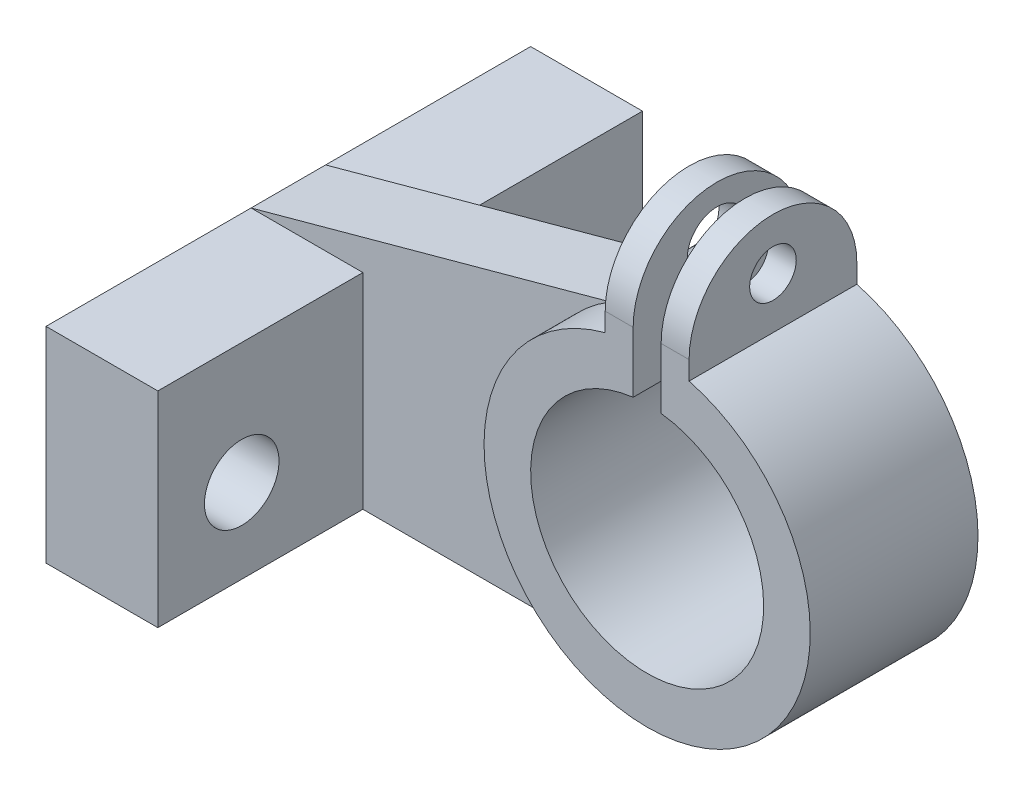
SolidWorks part; units mm, degrees
material "ABS"
ref_plane "Front Plane" through (0, 0, 0) normal (0, 0, 1) x (1, 0, 0)
ref_plane "Top Plane" through (0, 0, 0) normal (0, 1, 0) x (1, 0, 0)
ref_plane "Right Plane" through (0, 0, 0) normal (1, 0, 0) x (0, 0, -1)
sketch "Sketch1" plane through (0, 0, 0) normal (0, 0, 1) x (1, 0, 0)
  line L0 (-1.5, 27.9097) -> (-1.5, 12.4097)
  line L5 (-1.5, 27.9097) -> (-4.5, 27.9097)
  line L8 (-4.5, 27.9097) -> (-4.5, 16.9115)
  line L9 (1.5, 27.9097) -> (4.5, 27.9097)
  line L12 (4.5, 27.9097) -> (4.5, 16.9115)
  line L13 (1.5, 27.9097) -> (1.5, 12.4097)
  line L14 (-47.5, 4.5) -> (-8.9183, 15.057)
  line L15 (0, -17.5) -> (-41.5, -17.5)
  line L20 (-41.5, 4.5) -> (-41.5, -17.5)
  line L21 (-41.5, -17.5) -> (-47.5, -17.5)
  line L23 (-41.5, 4.5) -> (-47.5, 4.5)
  line L24 (-47.5, -17.5) -> (-47.5, 4.5)
  arc A0 (-1.5, 12.4097) -> (1.5, 12.4097) centre (0, 0) ccw
  arc A1 (-4.5, 16.9115) -> (4.5, 16.9115) centre (0, 0) ccw
  dimension "D1" = 25
  dimension "D2" = 5
  dimension "D3" = 3
  dimension "D4" = 9
  dimension "D5" = 3
  dimension "D6" = 3
  dimension "D7" = 15.5
  dimension "D8" = 40
  dimension "D9" = 6
  dimension "D10" = 41.5
  dimension "D11" = 22
  dimension "D12" = 17.5
extrude "Boss-Extrude1" add sketch "Sketch1" along normal blind 26 and the other way blind 26 contours L24 L21 L20 L23 | A1 L14 L23 L20 L15 | L8 A1 L12 L9 L13 A0 L0 L5 region at (-2.0733, 20.1597, 0) region at (-27.2359, -4.2234, 0) region at (-44.5, -6.5, 0)
ref_plane "Plane1" through (24.5, 0, 0) normal (1, 0, 0) x (0, 0, -1)
sketch "Sketch2" plane through (24.5, 0, 0) normal (1, 0, 0) x (0, 0, -1)
  line L0 (26, -17.5) -> (-26, -17.5) construction
  line L1 (-9, -17.5) -> (-26, -17.5)
  line L2 (-9, -17.5) -> (-9, 27.9097)
  line L3 (-9, 27.9097) -> (-26, 27.9097)
  line L4 (-26, -17.5) -> (-26, 27.9097)
  line L5 (26, 27.9097) -> (-26, 27.9097) construction
  line L6 (26, -17.5) -> (9, -17.5)
  line L7 (26, -17.5) -> (26, 27.9097)
  line L8 (26, 27.9097) -> (9, 27.9097)
  line L9 (9, -17.5) -> (9, 27.9097)
  dimension "D1" = 9
  dimension "D2" = 9
extrude "Cut-Extrude1" cut sketch "Sketch2" against normal blind 60
sketch "Sketch3" plane through (-47.5, 0, 0) normal (-1, 0, 0) x (0, 0, 1)
  line L0 (-26, -17.5) -> (-26, 4.5) construction
  line L1 (26, -17.5) -> (26, 4.5) construction
  line L2 (-26, -17.5) -> (26, -17.5) construction
  circle A0 centre (-17, -8.5) radius 4
  circle A1 centre (17, -8.5) radius 4
  dimension "D1" = 9
  dimension "D5" = 8
  dimension "D2" = 9
  dimension "D3" = 9
  dimension "D4" = 9
extrude "Cut-Extrude2" cut sketch "Sketch3" against normal up to vertex (12 mm away) up to point (-35.5, -17.5, 26)
ref_plane "Plane2" through (0, 22.5, 0) normal (0, -1, 0) x (-1, 0, 0)
sketch "Sketch4" plane through (0, 22.5, 0) normal (0, -1, 0) x (-1, 0, 0)
  line L1 (47.5, 26) -> (35.5, 26)
  line L2 (47.5, 26) -> (47.5, 4)
  line L3 (47.5, 4) -> (35.5, 4)
  line L4 (35.5, 26) -> (35.5, 4)
  line L5 (47.5, -26) -> (35.5, -26)
  line L6 (47.5, -26) -> (47.5, -4)
  line L7 (47.5, -4) -> (35.5, -4)
  line L8 (35.5, -26) -> (35.5, -4)
  line L10 (0, 0) -> (47.5, 0) construction
  line L11 (47.5, 26) -> (47.5, -26) construction
  dimension "D1" = 12
  dimension "D2" = 12
  dimension "D3" = 22
  dimension "D4" = 22
extrude "Cut-Extrude4" cut sketch "Sketch4" along normal blind 18
sketch "Sketch5" plane through (0, 0, 9) normal (0, 0, 1) x (1, 0, 0)
  line L0 (-47.5, 4.5) -> (-16.9115, 4.5)
  line L1 (-47.5, 4.5) -> (-8.9183, 15.057)
  arc A0 (-8.9183, 15.057) -> (-16.9115, 4.5) centre (0, 0) ccw
  dimension "D1" = 35
  dimension "D2" = 40
extrude "Cut-Extrude5" cut sketch "Sketch5" against normal blind 5
sketch "Sketch7" plane through (0, 0, -9) normal (0, 0, -1) x (-1, 0, 0)
  line L0 (47.5, 4.5) -> (16.9115, 4.5)
  line L1 (47.5, 4.5) -> (8.9183, 15.057)
  arc A0 (16.9115, 4.5) -> (8.9183, 15.057) centre (0, 0) ccw
  dimension "D1" = 35
  dimension "D2" = 40
extrude "Cut-Extrude6" cut sketch "Sketch7" against normal blind 5
sketch "Sketch8" plane through (4.5, 0, 0) normal (1, 0, 0) x (0, 0, -1)
  line L0 (0, 16.9115) -> (0, 27.9097) construction
  line L3 (9, 16.9115) -> (-9, 16.9115) construction
  line L4 (9, 27.9097) -> (-9, 27.9097) construction
  circle A0 centre (0, 22.4106) radius 2.5
  dimension "D1" = 5
  dimension "D2" = 5.4991
extrude "Cut-Extrude7" cut sketch "Sketch8" against normal up to vertex (3 mm away) up to point (1.5, 27.9097, 9)
sketch "Sketch15" plane through (-4.5, 0, 0) normal (-1, 0, 0) x (0, 0, 1)
  line L0 (0, 27.9097) -> (0, 16.9115) construction
  line L1 (-9, 27.9097) -> (9, 27.9097) construction
  line L2 (-9, 16.9115) -> (9, 16.9115) construction
  circle A0 centre (0, 22.4106) radius 3.2
  dimension "D1" = 6.4
sketch "Sketch9" plane through (0, 4.5, 0) normal (0, 1, 0) x (1, 0, 0)
  line L0 (-16.9115, 4) -> (-47.5, 4) construction
  line L1 (-16.9115, 9) -> (-35.5, 9)
  line L2 (-16.9115, 9) -> (-16.9115, 4)
  line L3 (-16.9115, 4) -> (-35.5, 4)
  line L4 (-35.5, 9) -> (-35.5, 4)
  line L5 (-47.5, -4) -> (-16.9115, -4) construction
  line L6 (-16.9115, -9) -> (-35.5, -9)
  line L7 (-16.9115, -9) -> (-16.9115, -4)
  line L8 (-16.9115, -4) -> (-35.5, -4)
  line L9 (-35.5, -9) -> (-35.5, -4)
  line L11 (-35.5, 9) -> (-35.5, -9) construction
extrude "Cut-Extrude8" cut sketch "Sketch9" against normal up to vertex (22 mm away) up to point (-35.5, -17.5, 9)
fillet "Fillet2" 2 edges at (-3, 27.9097, 9) (-3, 27.9097, -9) type full round first side face at (-1.8536, 10.415, 9) second side face at (-1.8536, 10.415, -9) middle face at (-3, 27.9097, 0)
fillet "Fillet3" 2 edges at (3, 27.9097, 9) (3, 27.9097, -9) type full round first side face at (-1.8536, 8.7786, 9) second side face at (-1.8536, 8.7786, -9) middle face at (3, 27.9097, 0)
sketch "Sketch10" plane through (0, 0, 9) normal (0, 0, 1) x (1, 0, 0)
  line L0 (0, -17.5) -> (-16.9115, -17.5)
  line L1 (-16.9115, -17.5) -> (-16.9115, -4.5)
  line L2 (-16.9115, -17.5) -> (-16.9115, 4.5) construction
  arc A0 (-16.9115, -4.5) -> (0, -17.5) centre (0, 0) ccw
  dimension "D1" = 35
extrude "Cut-Extrude9" cut sketch "Sketch10" against normal up to vertex (5 mm away) up to point (-16.9115, 4.5, 4)
sketch "Sketch11" plane through (0, 0, 9) normal (0, 0, 1) x (1, 0, 0)
  circle A0 centre (0, 0) radius 12.5
  circle A1 centre (0, 0) radius 17.5
  dimension "D1" = 25
  dimension "D2" = 35
extrude "Boss-Extrude2" add sketch "Sketch11" against normal up to vertex (5 mm away) up to point (-16.9115, 4.5, 4)
sketch "Sketch12" plane through (0, 0, -9) normal (0, 0, -1) x (-1, 0, 0)
  line L0 (0, -17.5) -> (16.9115, -17.5)
  line L1 (16.9115, -17.5) -> (16.9115, -4.5)
  line L2 (16.9115, -17.5) -> (16.9115, 4.5) construction
  arc A0 (0, -17.5) -> (16.9115, -4.5) centre (0, 0) ccw
  dimension "D1" = 35
extrude "Cut-Extrude10" cut sketch "Sketch12" against normal up to vertex (5 mm away) up to point (-16.9115, -17.5, -4)
sketch "Sketch13" plane through (0, 0, -9) normal (0, 0, -1) x (-1, 0, 0)
  circle A0 centre (0, 0) radius 12.5
  circle A1 centre (0, 0) radius 17.5
  dimension "D1" = 25
  dimension "D2" = 35
extrude "Boss-Extrude3" add sketch "Sketch13" against normal up to vertex (5 mm away) up to point (-16.9115, 4.5, -4)
sketch "Sketch14" plane through (0, 0, 9) normal (0, 0, 1) x (1, 0, 0)
  line L1 (-1.5, 18.9097) -> (1.5, 18.9097)
  line L2 (-1.5, 18.9097) -> (-1.5, 12.4097)
  line L3 (-1.5, 12.4097) -> (1.5, 12.4097)
  line L4 (1.5, 18.9097) -> (1.5, 12.4097)
extrude "Cut-Extrude11" cut sketch "Sketch14" against normal up to vertex (18 mm away) up to point (-1.5, 17.4356, -9)
extrude "Cut-Extrude12" cut sketch "Sketch15" against normal up to vertex (3 mm away) up to point (-1.5, 18.9097, 9)
